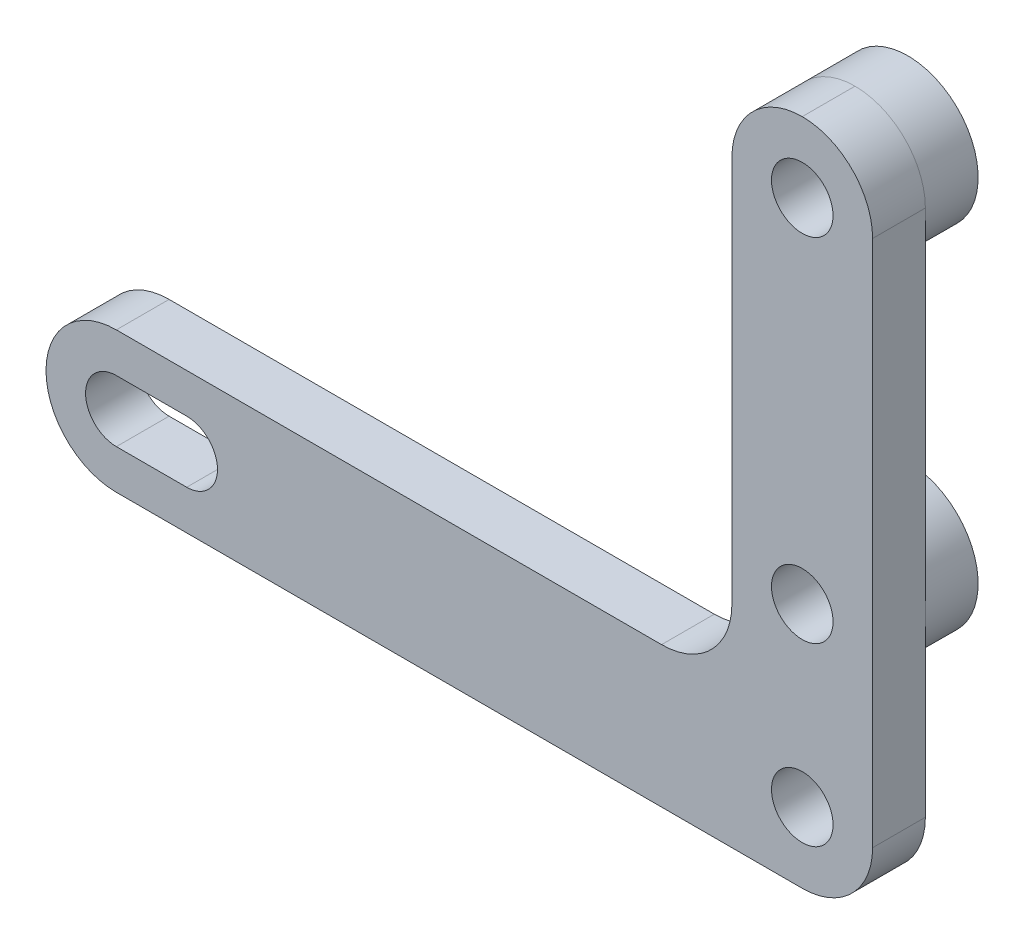
SolidWorks part; units mm, degrees
ref_plane "Plano frontal" through (0, 0, 0) normal (0, 0, 1) x (1, 0, 0)
ref_plane "Plano superior" through (0, 0, 0) normal (0, 1, 0) x (1, 0, 0)
ref_plane "Plano direito" through (0, 0, 0) normal (1, 0, 0) x (0, 0, -1)
sketch "Esboço1" plane through (0, 0, 0) normal (0, 0, 1) x (1, 0, 0)
  line L0 (4, -4) -> (-43, -4)
  line L1 (-4, 34) -> (4, 34)
  line L2 (-4, 34) -> (-4, 4)
  line L3 (-39, -1.75) -> (-35, -1.75)
  line L4 (4, 34) -> (4, -4)
  line L5 (-4, 34) -> (0.4706, -4) construction
  line L6 (-0.4706, -4) -> (4, 34) construction
  line L7 (-43, -4) -> (-43, 4)
  line L8 (-43, 4) -> (-4, 4)
  line L10 (-39, 1.75) -> (-35, 1.75)
  arc A0 (-39, 1.75) -> (-39, -1.75) centre (-39, 0) ccw
  circle A1 centre (0, 10) radius 1.75
  circle A2 centre (0, 30) radius 1.75
  circle A3 centre (0, 0) radius 1.75
  arc A4 (-35, -1.75) -> (-35, 1.75) centre (-35, 0) ccw
  point P0 (0, 0)
  point P11 (-43, 0)
  point P20 (0, 34)
  dimension "D1" = 39
  dimension "D3" = 3.5
  dimension "D5" = 20
  dimension "D2" = 4
  dimension "D4" = 8
  dimension "D6" = 4
  dimension "D7" = 10
  dimension "D8" = 4
extrude "Ressalto-extrusão1" add sketch "Esboço1" along normal blind 3
sketch "Esboço2" plane through (0, 0, 0) normal (0, 0, -1) x (-1, 0, 0)
  circle A0 centre (0, 30) radius 4
  circle A1 centre (0, 10) radius 4
  circle A2 centre (0, 30) radius 1.75
  circle A3 centre (0, 10) radius 1.75
  circle A6 centre (0, 30) radius 1.75 construction
  dimension "D1" = 8
extrude "Ressalto-extrusão2" add sketch "Esboço2" along normal blind 3
fillet "Filete1" radius 4 6 edges at (4, 34, 1.5) (-4, 34, 1.5) (-4, 4, 1.5) (4, -4, 1.5) (-43, -4, 1.5) (-43, 4, 1.5) tangent propagation no
